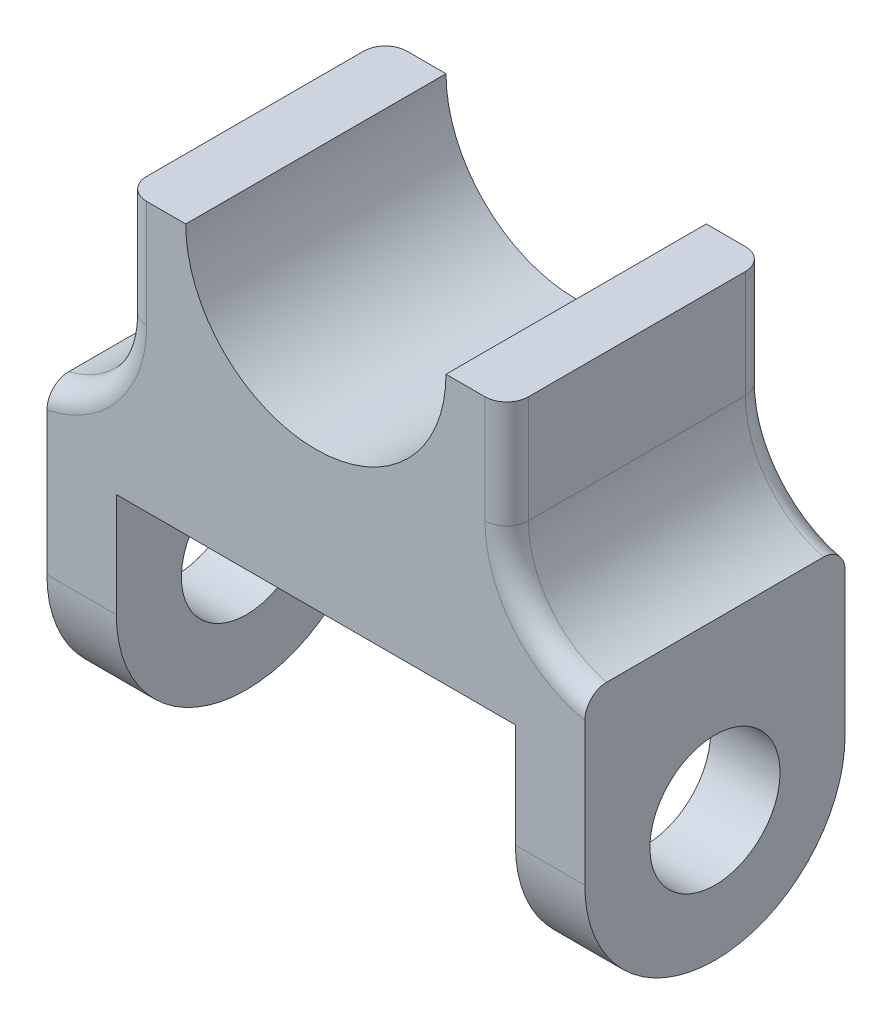
SolidWorks part; units mm, degrees
ref_plane "Front Plane" through (0, 0, 0) normal (0, 0, 1) x (1, 0, 0)
ref_plane "Top Plane" through (0, 0, 0) normal (0, 1, 0) x (1, 0, 0)
ref_plane "Right Plane" through (0, 0, 0) normal (1, 0, 0) x (0, 0, -1)
sketch "Sketch1" plane through (0, 0, 0) normal (0, 0, 1) x (1, 0, 0)
  line L0 (108, 0) -> (124, 0)
  line L1 (18, 116) -> (32, 116)
  line L2 (0, 68) -> (0, 0)
  line L3 (0, 0) -> (16, 0)
  line L4 (124, 68) -> (124, 0)
  line L5 (16, 54) -> (108, 54)
  line L6 (16, 54) -> (16, 0)
  line L8 (108, 54) -> (108, 0)
  line L9 (-27.4304, 30) -> (78.9349, 30) construction
  line L10 (-33.7989, 68) -> (158.1502, 68) construction
  line L11 (92, 116) -> (106, 116)
  line L12 (18, 153.7968) -> (18, 129.0689) construction
  line L13 (106, 153.7968) -> (106, 129.0689) construction
  line L14 (-63.0393, 116) -> (0, 116) construction
  line L16 (106, 91.2379) -> (106, 116)
  line L17 (18, 116) -> (106, 116) construction
  line L18 (18, 91.2379) -> (18, 116)
  arc A0 (32, 116) -> (92, 116) centre (62, 116) ccw
  arc A1 (18, 91.2379) -> (0, 68) centre (-6, 91.2379) cw
  arc A2 (124, 68) -> (106, 91.2379) centre (130, 91.2379) cw
  dimension "D5" = 30
  dimension "D12" = 24
  dimension "D13" = 24
  dimension "D1" = 124
  dimension "D2" = 86
  dimension "D3" = 16
  dimension "D4" = 16
  dimension "D6" = 54
  dimension "D7" = 46
  dimension "D8" = 30
  dimension "D9" = 38
  dimension "D10" = 14
  dimension "D11" = 14
extrude "Boss-Extrude1" add sketch "Sketch1" along normal blind 30 and the other way blind 30 contours A0 L11 L16 A2 L4 L0 L8 L5 L6 L3 L2 A1 L18 L1
fillet "Fillet1" radius 5 8 edges at (12.9737, 76.541, 30) (18, 103.619, 30) (12.9737, 76.541, -30) (18, 103.619, -30) (111.0263, 76.541, -30) (106, 103.619, -30) (106, 103.619, 30) (111.0263, 76.541, 30)
sketch "Sketch2" plane through (124, 0, 0) normal (1, 0, 0) x (0, 0, -1)
  line L0 (-44.038, 30) -> (59.5992, 30) construction
  line L1 (30, 0) -> (-30, 0) construction
  line L2 (0, 113.0451) -> (0, 14.7765) construction
  line L3 (-30, 62.8654) -> (-30, 0) construction
  circle A0 centre (0, 30) radius 15
  point P10 (0, 0)
  point P11 (0, 0)
  dimension "D3" = 30
  dimension "D1" = 30
  dimension "D2" = 30
extrude "Cut-Extrude1" cut sketch "Sketch2" against normal blind 124 contours A0
fillet "Fillet2" radius 30 4 edges at (116, 0, -30) (116, 0, 30) (8, 0, -30) (8, 0, 30)
